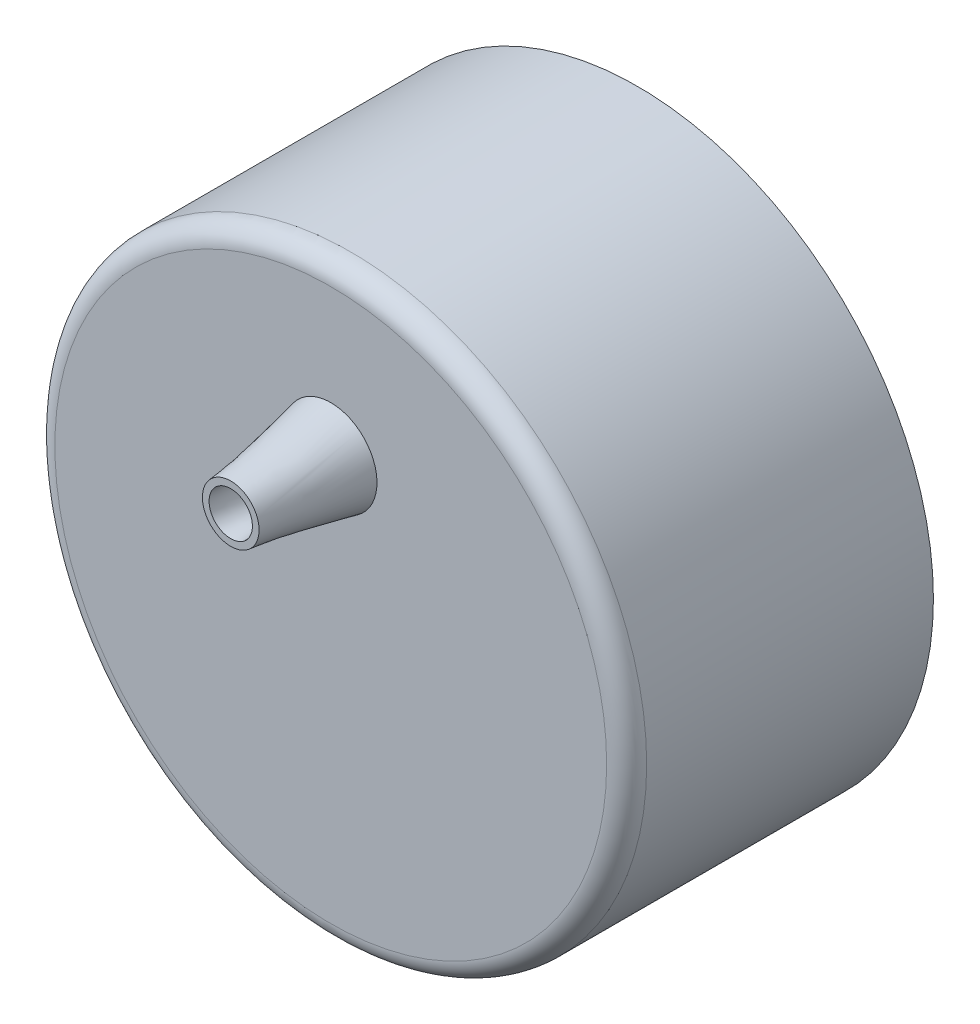
SolidWorks part; units mm, degrees
ref_plane "Front Plane" through (0, 0, 0) normal (0, 0, 1) x (1, 0, 0)
ref_plane "Top Plane" through (0, 0, 0) normal (0, 1, 0) x (1, 0, 0)
ref_plane "Right Plane" through (0, 0, 0) normal (1, 0, 0) x (0, 0, -1)
sketch "Sketch2" plane through (0, 0, 0) normal (0, 0, 1) x (1, 0, 0)
  circle A1 centre (177.5651, -76.6062) radius 41.375
  circle A2 centre (177.5651, -76.6062) radius 44.375
  dimension "D1" = 82.75
  dimension "D2" = 3
extrude "Boss-Extrude1" add sketch "Sketch2" along normal blind 40
sketch "Sketch3" plane through (0, 0, 40) normal (0, 0, 1) x (1, 0, 0)
  circle A0 centre (177.5651, -76.6062) radius 44.375 construction
  circle A1 centre (177.5651, -76.6062) radius 44.375
extrude "Boss-Extrude2" add sketch "Sketch3" along normal blind 6
fillet "Fillet1" radius 7 1 edges at (218.9401, -76.6062, 40)
fillet "Fillet2" radius 3 1 edges at (221.9401, -76.6062, 46)
sketch "Sketch4" plane through (0, 0, 0) normal (0, 0, 1) x (1, 0, 0)
  line L0 (177.5651, -35.2312) -> (177.5651, -117.9812) construction
  line L2 (218.9401, -76.6062) -> (136.1901, -76.6062) construction
  circle A0 centre (177.5651, -76.6062) radius 41.375 construction
  circle A1 centre (177.5651, -57.2312) radius 4.93
  circle A2 centre (177.5651, -57.2312) radius 6.93
  dimension "D2" = 9.86
  dimension "D3" = 2
  dimension "D1" = 22
ref_plane "Plane1" through (0, 0, 61) normal (0, 0, 1) x (1, 0, 0)
sketch "Sketch5" plane through (0, 0, 61) normal (0, 0, 1) x (1, 0, 0)
  circle A4 centre (177.5651, -57.2312) radius 3.25
  circle A5 centre (177.5651, -57.2312) radius 4.25
  dimension "D1" = 6.5
  dimension "D2" = 8.5
sketch "Sketch7" plane through (0, 0, 46) normal (0, 0, 1) x (1, 0, 0)
  circle A0 centre (177.5651, -57.2312) radius 6.93 construction
  circle A1 centre (177.5651, -57.2312) radius 6.93
  circle A2 centre (177.5651, -57.2312) radius 4.93 construction
  circle A3 centre (177.5651, -57.2312) radius 4.93
loft "Loft2" add section "Sketch7" section "Sketch5" connector at (181.8946, -51.8201, 46) connector at (181.5565, -55.7715, 61)
loft "Cut-Loft2" cut section "Sketch7<4>" section "Sketch5<6>" connector at (178.5648, -52.4036, 46) connector at (180.7863, -56.7995, 61)
sketch "Sketch7<4>" plane through (0, 0, 46) normal (0, 0, 1) x (1, 0, 0) same geometry as "Sketch7"
sketch "Sketch5<6>" plane through (0, 0, 61) normal (0, 0, 1) x (1, 0, 0) same geometry as "Sketch5"
extrude "Cut-Extrude1" cut sketch "Sketch7<5>" against normal up to next (6 mm away) contours A3 region at (177.5651, -57.2312, 46)
sketch "Sketch7<5>" plane through (0, 0, 46) normal (0, 0, 1) x (1, 0, 0) same geometry as "Sketch7"
